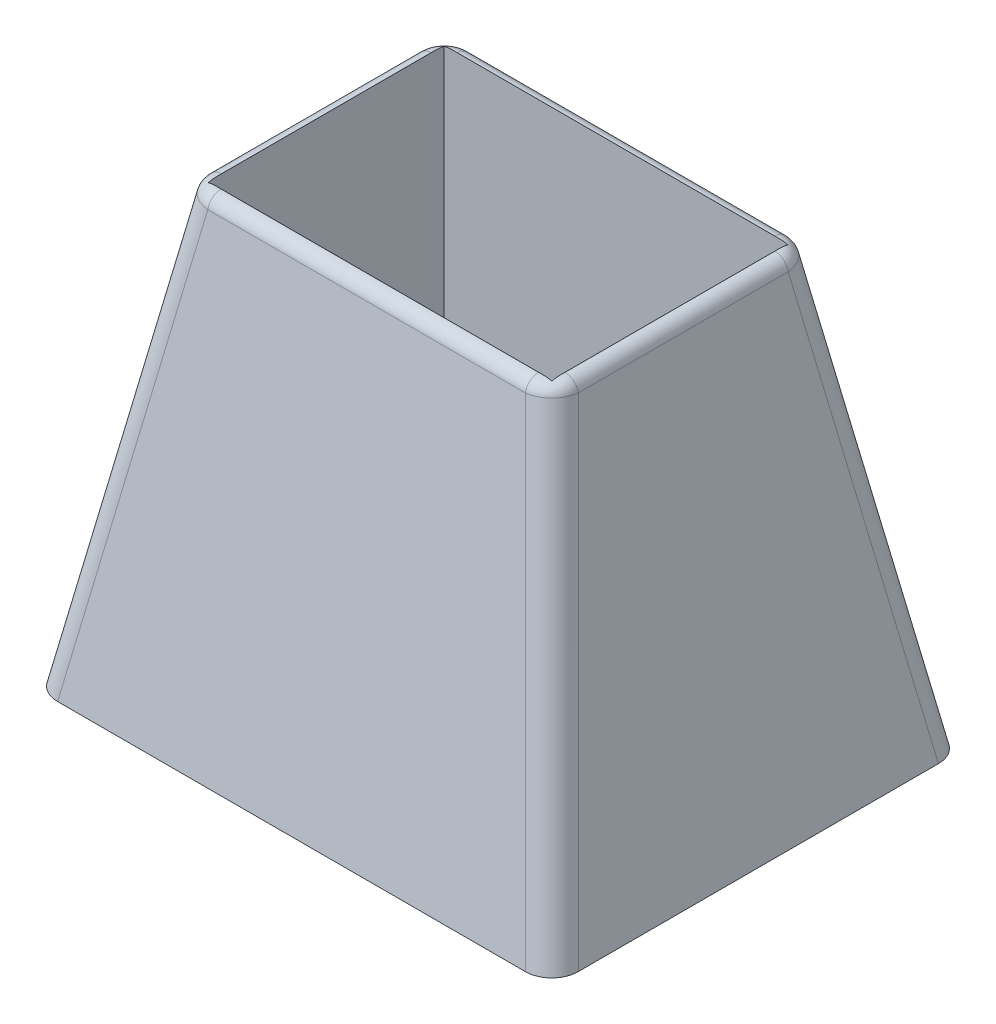
SolidWorks part; units mm, degrees
ref_plane "Front Plane" through (0, 0, 0) normal (0, 0, 1) x (1, 0, 0)
ref_plane "Top Plane" through (0, 0, 0) normal (0, 1, 0) x (1, 0, 0)
ref_plane "Right Plane" through (0, 0, 0) normal (1, 0, 0) x (0, 0, -1)
sketch "Sketch1" plane through (0, 0, 0) normal (0, 1, 0) x (1, 0, 0)
  line L1 (0, 0) -> (54.5, 0)
  line L2 (0, 0) -> (0, -38.5)
  line L3 (0, -38.5) -> (54.5, -38.5)
  line L4 (54.5, 0) -> (54.5, -38.5)
  dimension "D1" = 54.5
  dimension "D2" = 38.5
extrude "Boss-Extrude1" add sketch "Sketch1" against normal blind 65 draft 10 draft outward yes
sketch "Esboço3" plane through (0, 0, 0) normal (0, 1, 0) x (1, 0, 0)
  line L0 (0, -38.5) -> (54.5, -38.5) construction
  line L1 (1.7, -1.7) -> (52.8, -1.7)
  line L2 (1.7, -1.7) -> (1.7, -36.8)
  line L3 (1.7, -36.8) -> (52.8, -36.8)
  line L4 (52.8, -1.7) -> (52.8, -36.8)
  line L5 (54.5, -38.5) -> (54.5, 0) construction
  dimension "D1" = 51.1
  dimension "D2" = 35.1
  dimension "D3" = 1.7
  dimension "D4" = 1.7
extrude "Corte-extrusão1" cut sketch "Esboço3" against normal blind 60
sketch "Esboço4" plane through (0, -60, 0) normal (0, 1, 0) x (1, 0, 0)
  line L0 (1.7, -1.7) -> (1.7, -36.8) construction
  line L1 (52.8, -36.8) -> (52.8, -1.7) construction
  line L2 (52.8, -1.7) -> (1.7, -1.7) construction
  line L3 (52.8, -1.7) -> (1.7, -1.7) construction
  line L4 (24.25, -6.7) -> (30.25, -6.7)
  line L5 (24.25, -6.7) -> (24.25, -24.7)
  line L6 (24.25, -24.7) -> (30.25, -24.7)
  line L7 (30.25, -6.7) -> (30.25, -24.7)
  line L8 (1.7, -19.25) -> (52.8, -19.25) construction
  line L9 (52.8, -36.8) -> (52.8, -1.7) construction
  circle A0 centre (5, -5.7) radius 2.5
  circle A1 centre (49.5, -5) radius 2.5
  circle A2 centre (49.5, -33.5) radius 2.5
  circle A3 centre (5, -32.8) radius 2.5
  dimension "D1" = 5
  dimension "D2" = 5
  dimension "D6" = 4
  dimension "D3" = 3.3
  dimension "D4" = 3.3
  dimension "D5" = 3.3
  dimension "D7" = 6
  dimension "D8" = 18
  dimension "D9" = 5
  dimension "D10" = 19.25
extrude "Corte-extrusão2" cut sketch "Esboço4" against normal through all
fillet "Filete1" radius 4 4 edges at (60.2306, -32.5, 44.2306) (60.2306, -32.5, -5.7306) (-5.7306, -32.5, -5.7306) (-5.7306, -32.5, 44.2306)
fillet "Filete2" radius 2 8 edges at (1.1467, 0, 37.3533) (1.1467, 0, 1.1467) (53.3533, 0, 1.1467) (53.3533, 0, 37.3533) (54.5, 0, 19.25) (27.25, 0, 0) (0, 0, 19.25) (27.25, 0, 38.5)
